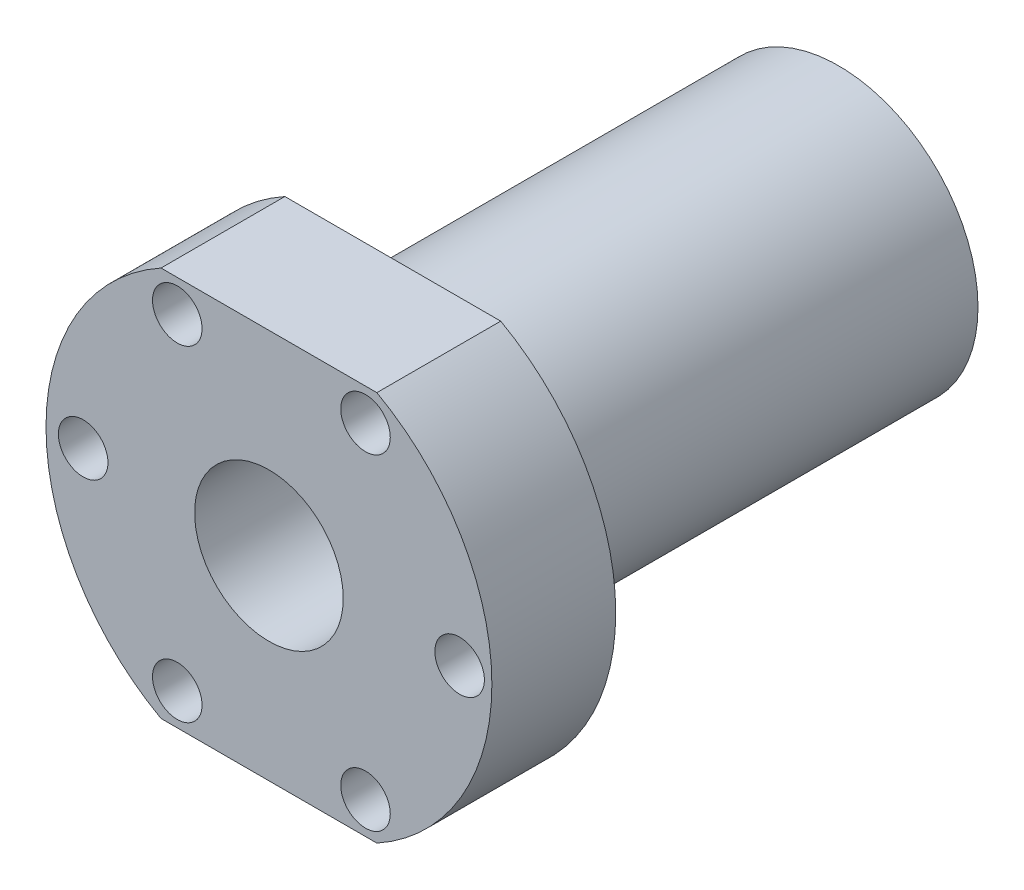
SolidWorks part; units mm, degrees
ref_plane "Alzado" through (0, 0, 0) normal (0, 0, 1) x (1, 0, 0)
ref_plane "Planta" through (0, 0, 0) normal (0, 1, 0) x (1, 0, 0)
ref_plane "Vista lateral" through (0, 0, 0) normal (1, 0, 0) x (0, 0, -1)
sketch "Croquis1" plane through (0, 0, 0) normal (0, 0, 1) x (1, 0, 0)
  line L0 (-8.7142, -15.75) -> (8.7142, -15.75)
  line L1 (8.7142, 15.75) -> (-8.7142, 15.75)
  arc A0 (-8.7142, 15.75) -> (-8.7142, -15.75) centre (0, 0) ccw
  arc A1 (8.7142, -15.75) -> (8.7142, 15.75) centre (0, 0) ccw
  dimension "D1" = 36
  dimension "D2" = 31.5
  dimension "D3" = 15.75
extrude "Saliente-Extruir1" add sketch "Croquis1" along normal blind 10
sketch "Croquis2" plane through (0, 0, 10) normal (0, 0, 1) x (1, 0, 0)
  circle A0 centre (-15, 0) radius 2
  dimension "D1" = 4
  dimension "D2" = 15
extrude "Cortar-Extruir1" cut sketch "Croquis2" against normal blind 18
ref_point "Punto1"
ref_axis "Eje1" through (0.1979, 0, 10) along (0, 0, 1)
pattern_circular "MatrizC1" count 6 over 360 about axis through (0.1979, 0, 10) along (0, 0, 1) of "Cortar-Extruir1"
sketch "Croquis4" plane through (0, 0, 0) normal (0, 0, -1) x (-1, 0, 0)
  circle A0 centre (0, 0) radius 11.25
  dimension "D1" = 22.5
extrude "Saliente-Extruir2" add sketch "Croquis4" along normal blind 36
sketch "Croquis5" plane through (0, 0, 10) normal (0, 0, 1) x (1, 0, 0)
  circle A0 centre (0, 0) radius 6
  dimension "D1" = 12
extrude "Cortar-Extruir2" cut sketch "Croquis5" against normal blind 53
